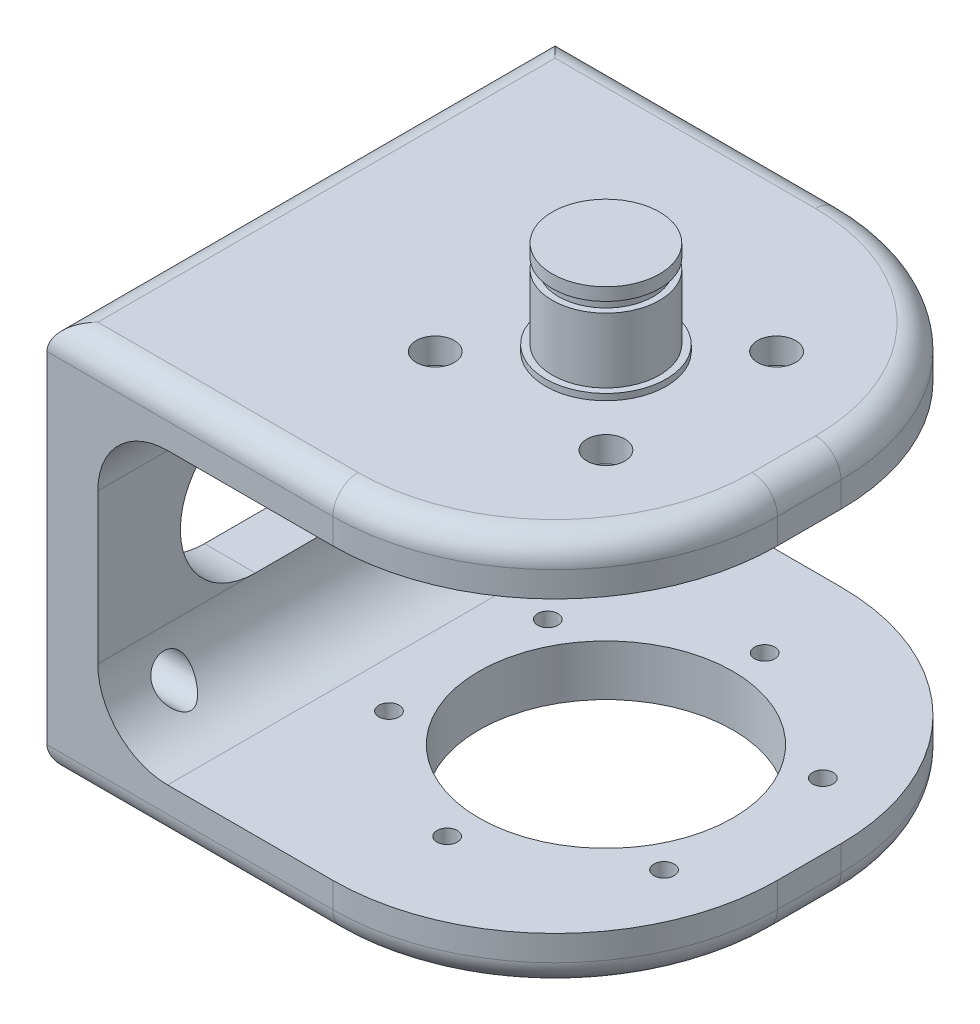
SolidWorks part; units mm, degrees
material "PETG-CF"
ref_plane "Front Plane" through (0, 0, 0) normal (0, 0, 1) x (1, 0, 0)
ref_plane "Top Plane" through (0, 0, 0) normal (0, 1, 0) x (1, 0, 0)
ref_plane "Right Plane" through (0, 0, 0) normal (1, 0, 0) x (0, 0, -1)
sketch "草图1" plane through (0, 0, 0) normal (0, 1, 0) x (1, 0, 0)
  line L1 (40, -40) -> (-40, -40)
  line L2 (40, -40) -> (40, 40)
  line L3 (40, 40) -> (-40, 40)
  line L4 (-40, -40) -> (-40, 40)
  line L5 (40, -40) -> (-40, 40) construction
  line L6 (40, 40) -> (-40, -40) construction
  point P0 (0, 0)
  dimension "D1" = 80
  dimension "D2" = 80
extrude "凸台-拉伸1" add sketch "草图1" along normal blind 8
sketch "草图2" plane through (0, 8, 0) normal (0, 1, 0) x (1, 0, 0)
  line L0 (-40, -40) -> (40, -40) construction
  line L1 (-32, -40) -> (-40, -40)
  line L2 (-32, -40) -> (-32, 40)
  line L3 (-32, 40) -> (-40, 40)
  line L4 (-40, -40) -> (-40, 40)
  line L5 (-32, -40) -> (-40, 40) construction
  line L6 (-32, 40) -> (-40, -40) construction
  point P0 (-36, 0)
  dimension "D1" = 8
extrude "凸台-拉伸2" add sketch "草图2" along normal blind 53.6
sketch "草图5" plane through (-32, 0, 0) normal (1, 0, 0) x (0, 0, -1)
  line L0 (-40, 61.6) -> (-40, 8) construction
  line L1 (40, 53.6) -> (-40, 53.6)
  line L2 (40, 53.6) -> (40, 61.6)
  line L3 (40, 61.6) -> (-40, 61.6)
  line L4 (-40, 53.6) -> (-40, 61.6)
  line L5 (40, 53.6) -> (-40, 61.6) construction
  line L6 (40, 61.6) -> (-40, 53.6) construction
  line L7 (40, 61.6) -> (40, 8) construction
  line L9 (-40, 61.6) -> (40, 61.6) construction
  point P0 (0, 57.6)
  dimension "D1" = 8
extrude "凸台-拉伸3" add sketch "草图5" along normal through all
sketch "草图4" plane through (0, 8, 0) normal (0, 1, 0) x (1, 0, 0)
  line L0 (-40, 40) -> (-40, -40) construction
  line L2 (40, -40) -> (40, 40) construction
  circle A0 centre (8, 0) radius 25 construction
  circle A1 centre (8, 25) radius 1.6
  circle A2 centre (-13.6506, 12.5) radius 1.6
  circle A3 centre (-13.6506, -12.5) radius 1.6
  circle A4 centre (8, -25) radius 1.6
  circle A5 centre (8, 0) radius 20
  circle A6 centre (29.6506, -12.5) radius 1.6
  circle A7 centre (29.6506, 12.5) radius 1.6
  point P17 (8, 0)
  point P22 (-40, 0)
  dimension "D3" = 50
  dimension "D4" = 3.2
  dimension "D6" = 40
  dimension "D1" = 32
  dimension "D5" = 6
extrude "切除-拉伸1" cut sketch "草图4" against normal through all contours A5 | A2 | A1 | A4 | A3 | A7 | A6
sketch "草图7" plane through (0, 61.6, 0) normal (0, 1, 0) x (1, 0, 0)
  line L0 (40, 40) -> (40, -40) construction
  line L3 (8, 0) -> (-5.435, 13.435) construction
  line L4 (8, 0) -> (8, 19) construction
  circle A0 centre (8, 0) radius 19 construction
  circle A5 centre (-5.435, 13.435) radius 1.6
  circle A6 centre (21.435, 13.435) radius 1.6
  circle A7 centre (21.435, -13.435) radius 1.6
  circle A8 centre (-5.435, -13.435) radius 1.6
  point P10 (40, 0)
  point P20 (8, 0)
  dimension "D1" = 38
  dimension "D4" = 45
  dimension "D5" = 3.2
  dimension "D6" = 4
extrude "切除-拉伸3" cut sketch "草图7" against normal up to next
fillet "圆角3" radius 35 4 edges at (40, 4, 40) (40, 4, -40) (40, 57.6, -40) (40, 57.6, 40)
fillet "圆角4" radius 11 2 edges at (-32, 8, 0) (-32, 53.6, 0)
sketch "草图6" plane through (-40, 0, 0) normal (-1, 0, 0) x (0, 0, 1)
  line L1 (30, 13) -> (-30, 13) construction
  line L2 (30, 13) -> (30, 48.6) construction
  line L3 (30, 48.6) -> (-30, 48.6) construction
  line L4 (-30, 13) -> (-30, 48.6) construction
  line L5 (30, 13) -> (-30, 48.6) construction
  line L6 (30, 48.6) -> (-30, 13) construction
  line L8 (40, 61.6) -> (40, 0) construction
  line L9 (-40, 61.6) -> (-40, 0) construction
  line L10 (-30, 30.8) -> (30, 30.8) construction
  line L11 (0, 13) -> (0, 48.6) construction
  line L12 (-40, 61.6) -> (40, 61.6) construction
  line L13 (-40, 0) -> (40, 0) construction
  circle A0 centre (-30, 48.6) radius 1.6
  circle A1 centre (30, 48.6) radius 1.6
  circle A2 centre (30, 13) radius 1.6
  circle A3 centre (-30, 13) radius 1.6
  point P0 (0, 30.8)
  dimension "D5" = 3.2
  dimension "D1" = 13
  dimension "D2" = 13
  dimension "D3" = 10
  dimension "D4" = 10
extrude "切除-拉伸2" cut sketch "草图6" against normal through all
sketch "草图8" plane through (0, 61.6, 0) normal (0, 1, 0) x (1, 0, 0)
  circle A0 centre (8, 0) radius 8.45
  dimension "D1" = 16.9
extrude "凸台-拉伸4" add sketch "草图8" along normal blind 14.8
ref_plane "基准面1" through (0, 74.4, 0) normal (0, 1, 0) x (1, 0, 0)
sketch "草图10" plane through (0, 74.4, 0) normal (0, 1, 0) x (1, 0, 0)
  circle A0 centre (8, 0) radius 8.45
  circle A1 centre (8, 0) radius 7.45
  dimension "D1" = 14.9
extrude "切除-拉伸4" cut sketch "草图10" against normal blind 1.6
ref_plane "基准面2" through (-36, 0, 0) normal (-1, 0, 0) x (0, 0, 1)
sketch "草图12" plane through (-36, 0, 0) normal (-1, 0, 0) x (0, 0, 1)
  line L0 (-40, 30.8) -> (40, 30.8) construction
  line L1 (-40, 61.6) -> (-40, 0) construction
  line L2 (40, 61.6) -> (40, 0) construction
  line L3 (0, 61.6) -> (0, 0) construction
  line L4 (8.45, 61.6) -> (-8.45, 61.6) construction
  circle A0 centre (-30, 48.6) radius 3
  circle A1 centre (30, 48.6) radius 3
  circle A2 centre (30, 13) radius 3
  circle A3 centre (-30, 13) radius 3
  dimension "D1" = 6
extrude "切除-拉伸5" cut sketch "草图12" against normal up to next
sketch "草图14" plane through (0, 61.6, 0) normal (0, 1, 0) x (1, 0, 0)
  circle A0 centre (-5.435, 13.435) radius 3
  circle A1 centre (21.435, 13.435) radius 3
  circle A2 centre (21.435, -13.435) radius 3
  circle A3 centre (-5.435, -13.435) radius 3
  point P12 (8, 0)
  dimension "D1" = 6
  dimension "D2" = 4
sketch "Sketch1" plane through (-32, 0, 0) normal (1, 0, 0) x (0, 0, -1)
  line L0 (15.2, 30.8) -> (-15.2, 30.8) construction
  line L1 (15.2, 19) -> (-15.2, 19)
  line L2 (15.2, 42.6) -> (-15.2, 42.6)
  line L3 (40, 42.6) -> (40, 19) construction
  line L4 (5, 61.6) -> (-5, 61.6) construction
  line L5 (40, 42.6) -> (-40, 42.6) construction
  arc A0 (15.2, 19) -> (15.2, 42.6) centre (15.2, 30.8) ccw
  arc A1 (-15.2, 42.6) -> (-15.2, 19) centre (-15.2, 30.8) ccw
  point P2 (0, 30.8)
  point P12 (40, 30.8)
  point P15 (0, 61.6)
  point P18 (27, 30.8)
  dimension "D1" = 13
extrude "Cut-Extrude1" cut sketch "Sketch1" against normal through all
extrude "切除-拉伸6" cut sketch "草图14" against normal blind 4
sketch "草图15" plane through (0, 0, 0) normal (0, -1, 0) x (1, 0, 0)
  circle A0 centre (-13.6506, 12.5) radius 3
  circle A1 centre (8, 25) radius 3
  circle A2 centre (29.6506, 12.5) radius 3
  circle A3 centre (29.6506, -12.5) radius 3
  circle A4 centre (8, -25) radius 3
  circle A5 centre (-13.6506, -12.5) radius 3
  point P15 (8, 0)
  dimension "D1" = 6
  dimension "D2" = 6
extrude "切除-拉伸7" cut sketch "草图15" against normal blind 4
sketch "草图16" plane through (0, 61.6, 0) normal (0, 1, 0) x (1, 0, 0)
  circle A0 centre (8, 0) radius 9.5
  dimension "D1" = 19
extrude "凸台-拉伸5" add sketch "草图16" along normal blind 1
fillet "Fillet2" radius 4 12 edges at (-17.5, 0, -40) (29.7487, 0, -29.7487) (40, 0, 0) (29.7487, 0, 29.7487) (-17.5, 61.6, 40) (-17.5, 61.6, -40) (29.7487, 61.6, -29.7487) (40, 61.6, 0) (-40, 61.6, 0) (-40, 0, 0) (-17.5, 0, 40) (29.7487, 61.6, 29.7487)
